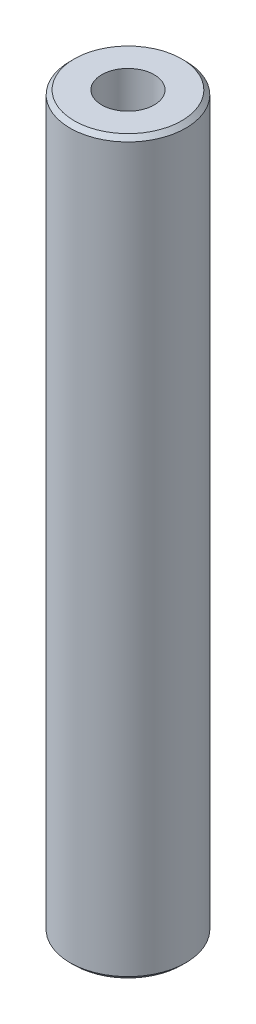
SolidWorks part; units mm, degrees
ref_plane "Front Plane" through (0, 0, 0) normal (0, 0, 1) x (1, 0, 0)
ref_plane "Top Plane" through (0, 0, 0) normal (0, 1, 0) x (1, 0, 0)
ref_plane "Right Plane" through (0, 0, 0) normal (1, 0, 0) x (0, 0, -1)
sketch "Sketch1" plane through (0, 0, 0) normal (0, 1, 0) x (1, 0, 0)
  circle A0 centre (0, 0) radius 47.5
  dimension "SHAFT_OD" = 95
extrude "Boss-Extrude1" add sketch "Sketch1" along normal blind 600
sketch "Sketch2" plane through (0, 0, 0) normal (0, 1, 0) x (1, 0, 0)
  circle A0 centre (0, 0) radius 21.5307
  dimension "BORE_D" = 43.0614
extrude "Cut-Extrude1" cut sketch "Sketch2" along normal through all
chamfer "Chamfer1" distance 3.4808 angle 44.766 2 edges at (0, 600, 47.5) (0, 0, 47.5) first distance on face at (0, 600, 47.5) first distance on face at (0, 0, 21.5307)
